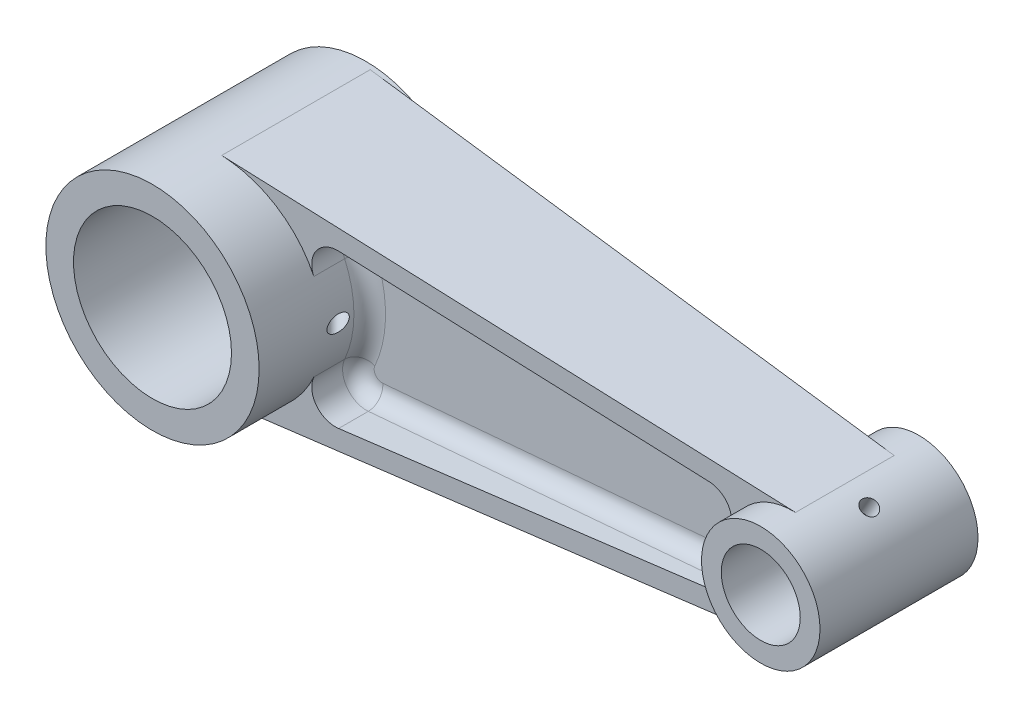
SolidWorks part; units mm, degrees
ref_plane "前视基准面" through (0, 0, 0) normal (0, 0, 1) x (1, 0, 0)
ref_plane "上视基准面" through (0, 0, 0) normal (0, 1, 0) x (1, 0, 0)
ref_plane "右视基准面" through (0, 0, 0) normal (1, 0, 0) x (0, 0, -1)
sketch "草图2" plane through (0, 0, 0) normal (0, 0, 1) x (1, 0, 0)
  circle A0 centre (0, 0) radius 13.5
  dimension "D1" = 27
extrude "凸台-拉伸1" add sketch "草图2" along normal blind 27
sketch "草图3" plane through (0, 0, 0) normal (0, 0, 1) x (1, 0, 0)
  circle A0 centre (70, 0) radius 7.5
  dimension "D1" = 15
  dimension "D2" = 70
extrude "凸台-拉伸2" add sketch "草图3" along normal blind 20 separate body
sketch "草图4" plane through (0, 0, 0) normal (0, 0, 1) x (1, 0, 0)
  line L0 (1.1571, 13.4503) -> (70.6429, 7.4724)
  line L1 (1.1571, -13.4503) -> (70.6429, -7.4724)
  circle A0 centre (70, 0) radius 7.5 construction
  circle A1 centre (0, 0) radius 13.5 construction
  circle A2 centre (70, 0) radius 7.5
  circle A3 centre (0, 0) radius 13.5
extrude "凸台-拉伸3" add sketch "草图4" against normal mid plane 6 from offset 10 contours A3 L1 A2 L0 region at (35.5922, 0, 0)
sketch "草图5" plane through (0, 0, 0) normal (0, 1, 0) x (1, 0, 0)
  line L0 (10, -1) -> (10, -19)
  line L1 (65, -3.5) -> (65, -16.5)
  line L2 (1.1571, -10) -> (70, -10) construction
  line L3 (1.1571, -7) -> (1.1571, -13) construction
  line L5 (0, -14.85) -> (0, 14.85) construction
  line L8 (77.5, -20) -> (77.5, 0) construction
  point P3 (10, -10)
  point P6 (65, -10)
  dimension "D1" = 10
  dimension "D2" = 7.5
  dimension "D3" = 5
  dimension "D4" = 18
  dimension "D5" = 13
ref_plane "基准面1" through (-0.0247, 0, 0.5443) normal (0.0454, 0, -0.999) x (-0.999, 0, -0.0454)
ref_plane "基准面2" through (0.8825, 0, 19.4144) normal (0.0454, 0, 0.999) x (0.999, 0, -0.0454)
sketch "草图6" plane through (0, 0, 7) normal (0, 0, -1) x (-1, 0, 0)
  line L0 (-64.859, -5.4608) -> (-8.7403, -10.2887)
  line L1 (-8.7403, 10.2887) -> (-64.859, 5.4608)
  line L2 (-1.1571, 13.4503) -> (-70.6429, 7.4724)
  line L3 (-70.6429, -7.4724) -> (-1.1571, -13.4503)
  line L4 (-1.1571, 13.4503) -> (-70.6429, 7.4724)
  line L5 (-70.6429, -7.4724) -> (-1.1571, -13.4503)
  line L6 (-70.4286, -4.9816) -> (-0.9429, -10.9595) construction
  line L7 (-0.9429, 10.9595) -> (-70.4286, 4.9816) construction
  arc A2 (-1.1571, 13.4503) -> (-1.1571, -13.4503) centre (0, 0) ccw
  arc A3 (-70.6429, -7.4724) -> (-70.6429, 7.4724) centre (-70, 0) ccw
  arc A4 (-1.1571, 13.4503) -> (-1.1571, -13.4503) centre (0, 0) ccw
  arc A5 (-70.6429, -7.4724) -> (-70.6429, 7.4724) centre (-70, 0) ccw
  arc M5 (-1.1571, -13.4503) -> (-1.1571, 13.4503) centre (0, 0) cw
  line M6 (-1.1571, 13.4503) -> (-70.6429, 7.4724)
  arc M7 (-70.6429, 7.4724) -> (-70.6429, -7.4724) centre (-70, 0) cw
  line M8 (-70.6429, -7.4724) -> (-1.1571, -13.4503)
  dimension "D1" = 0
  dimension "D2" = 2.5
extrude "凸台-拉伸4" add sketch "草图6" along normal up to surface and the other way up to surface contours L1 M5 M6 M7 | L0 M7 M8 M5 region at (36.5049, -9.191, 7) region at (36.5049, 9.191, 7) up to plane "基准面1" other way up to plane "基准面2"
fillet "圆角1" radius 3 8 edges at (64.859, 5.4608, 14.7532) (64.859, -5.4608, 14.7532) (8.7403, -10.2887, 16.0286) (8.7403, 10.2887, 16.0286) (64.859, 5.4608, 5.2468) (64.859, -5.4608, 5.2468) (8.7403, 10.2887, 3.9714) (8.7403, -10.2887, 3.9714)
sketch "草图7" plane through (0, 0, 27) normal (0, 0, 1) x (1, 0, 0)
  circle A0 centre (0, 0) radius 10
  dimension "D1" = 20
extrude "切除-拉伸1" cut sketch "草图7" against normal through all
sketch "草图8" plane through (0, 0, 20) normal (0, 0, 1) x (1, 0, 0)
  line L0 (1.1571, 0) -> (70, 0) construction
  line L1 (14.85, 0) -> (-14.85, 0) construction
  circle A0 centre (70, 0) radius 5
  dimension "D1" = 10
extrude "切除-拉伸2" cut sketch "草图8" against normal through all
ref_plane "基准面3" through (0, 0, 10) normal (0, 0, 1) x (1, 0, 0)
sketch "草图9" plane through (0, 0, 10) normal (0, 0, 1) x (1, 0, 0)
  line L0 (70, 0) -> (80.6127, 18.3818)
  line L1 (70, 0) -> (59.9674, -17.377)
  line L2 (14.85, 0) -> (-14.85, 0) construction
  dimension "D1" = 60
sweep "切除-扫描1" cut path "草图9" circular profile diameter 2 parameters "D3"=2
fillet "圆角2" radius 2 16 edges at (12.6186, 8.4721, 7) (13.5, 0, 7) (12.6186, -8.4721, 7) (37.7397, -7.7939, 7) (62.3712, -4.5794, 7) (62.5, 0, 7) (62.3712, 4.5794, 7) (37.7397, 7.7939, 7) (62.3712, -4.5794, 13) (37.7397, -7.7939, 13) (12.6186, -8.4721, 13) (13.5, 0, 13) (12.6186, 8.4721, 13) (37.7397, 7.7939, 13) (62.3712, 4.5794, 13) (62.5, 0, 13)
sketch "草图17" plane through (0, 0, 0) normal (0, 1, 0) x (1, 0, 0)
  line L0 (7.5, -11) -> (18.6173, -22.1173)
  line L2 (1.0653, -11) -> (7.5, -11) construction
  line L3 (7.5, -11) -> (18.1518, -0.3482)
  line L4 (13.5, -27) -> (13.5, 0) construction
  line L6 (-13.5, -27) -> (13.5, -27) construction
  point P5 (13.5, -17)
  point P10 (13.5, -5)
  point P11 (7.5, -11)
  dimension "D1" = 90
  dimension "D2" = 12
  dimension "D3" = 16
sweep "切除-扫描2" cut path "草图17" circular profile diameter 2 parameters "D3"=2
